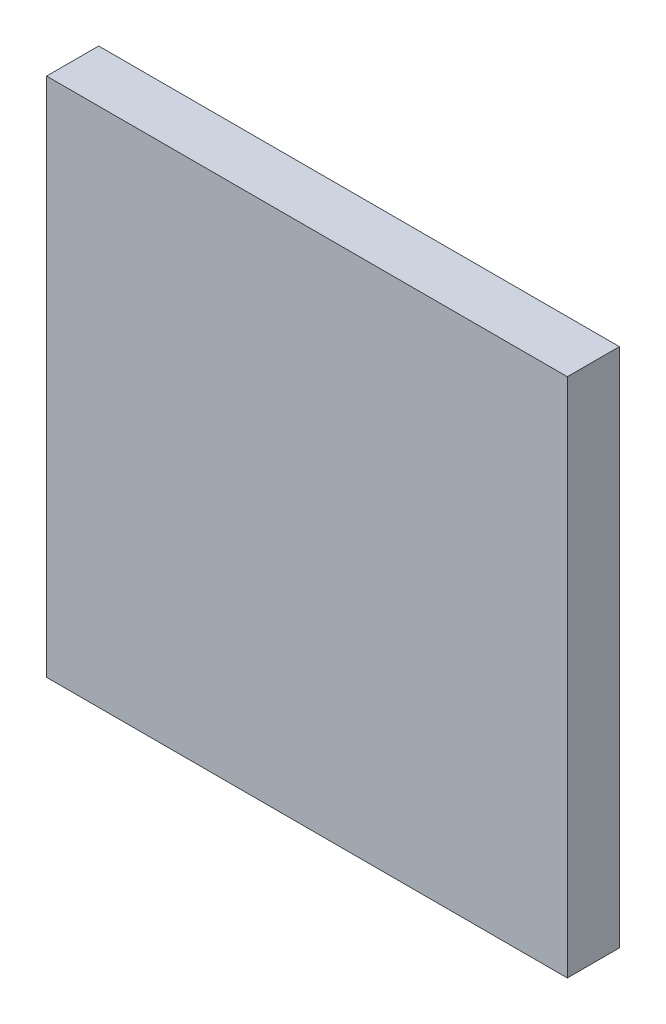
SolidWorks part; units mm, degrees
ref_plane "Ön Düzlem" through (0, 0, 0) normal (0, 0, 1) x (1, 0, 0)
ref_plane "Üst Düzlem" through (0, 0, 0) normal (0, 1, 0) x (1, 0, 0)
ref_plane "Sağ Düzlem" through (0, 0, 0) normal (1, 0, 0) x (0, 0, -1)
sketch "Çizim1" plane through (0, 0, 0) normal (0, 0, 1) x (1, 0, 0)
  line L1 (0, 0) -> (200, 0)
  line L2 (0, 0) -> (0, -200)
  line L3 (0, -200) -> (200, -200)
  line L4 (200, 0) -> (200, -200)
  dimension "D1" = 200
  dimension "D2" = 200
base flange "Taban-Flanş1" sketch "Çizim1" thickness 20 reverse thickness direction no parameters "D1"=6
sketch "Büküm-Çizgileri1" [suppressed] plane through (0, 0, 0) normal (0, 1, 0) x (1, 0, 0)
sketch "Sınırlandırma-Kutusu1" [suppressed] plane through (0, 0, 0) normal (0, 1, 0) x (1, 0, 0)
sheet metal parameters "Sac-Levha1" thickness 20 parameters "D1"=6
flat pattern "Düz-Çoğaltma1" [suppressed]
sketch "Büküm-Çizgileri2" plane through (0, 0, 0) normal (0, 1, 0) x (1, 0, 0)
sketch3d "Sınırlandırma-Kutusu2" [suppressed]
  line L0 (0, -200, 0) -> (200, -200, 0) construction
  line L1 (0, 0, 0) -> (200, 0, 0) construction
  line L2 (0, -200, 0) -> (0, 0, 0) construction
  line L3 (200, -200, 0) -> (200, 0, 0) construction
